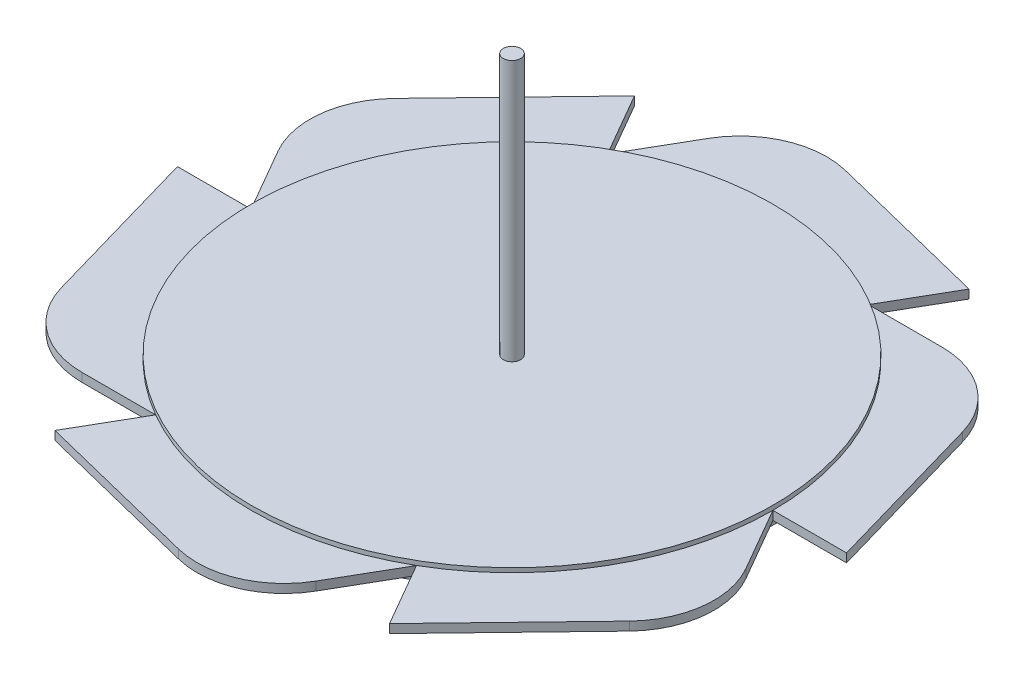
SolidWorks part; units mm, degrees
ref_plane "Front Plane" through (0, 0, 0) normal (0, 0, 1) x (1, 0, 0)
ref_plane "Top Plane" through (0, 0, 0) normal (0, 1, 0) x (1, 0, 0)
ref_plane "Right Plane" through (0, 0, 0) normal (1, 0, 0) x (0, 0, -1)
sketch "Sketch1" plane through (0, 0, 0) normal (0, 1, 0) x (1, 0, 0)
  line L0 (0, 0) -> (-7.5, 12.9904) construction
  line L1 (0, 0) -> (7.5, 12.9904) construction
  line L2 (-7.5, 12.9904) -> (7.5, 12.9904) construction
  line L3 (-7.5, 12.9904) -> (-5.3825, 16.658)
  line L4 (7.5, 12.9904) -> (9.6175, 16.658)
  line L5 (0.1538, 19.0104) -> (9.6175, 16.658)
  line L6 (7.5, 12.9904) -> (11.735, 12.9904)
  line L7 (16.5404, 9.372) -> (19.235, 0)
  line L8 (15, 0) -> (19.235, 0)
  line L9 (15, 0) -> (17.1175, -3.6677)
  line L10 (16.3866, -9.6384) -> (9.6175, -16.658)
  line L11 (7.5, -12.9904) -> (9.6175, -16.658)
  line L12 (7.5, -12.9904) -> (5.3825, -16.658)
  line L13 (-0.1538, -19.0104) -> (-9.6175, -16.658)
  line L14 (-7.5, -12.9904) -> (-9.6175, -16.658)
  line L15 (-7.5, -12.9904) -> (-11.735, -12.9904)
  line L16 (-16.5404, -9.372) -> (-19.235, 0)
  line L17 (-15, 0) -> (-19.235, 0)
  line L18 (-15, 0) -> (-17.1175, 3.6677)
  line L19 (-16.3866, 9.6384) -> (-9.6175, 16.658)
  line L20 (-7.5, 12.9904) -> (-9.6175, 16.658)
  circle A0 centre (0, 0) radius 15
  arc A1 (-5.3825, 16.658) -> (0.1538, 19.0104) centre (-1.0523, 14.158) cw
  arc A2 (11.735, 12.9904) -> (16.5404, 9.372) centre (11.735, 7.9904) cw
  arc A3 (17.1175, -3.6677) -> (16.3866, -9.6384) centre (12.7874, -6.1677) cw
  arc A4 (5.3825, -16.658) -> (-0.1538, -19.0104) centre (1.0523, -14.158) cw
  arc A5 (-11.735, -12.9904) -> (-16.5404, -9.372) centre (-11.735, -7.9904) cw
  arc A6 (-17.1175, 3.6677) -> (-16.3866, 9.6384) centre (-12.7874, 6.1677) cw
  point P9 (-3.5, 19.9186)
  point P42 (0, 0)
  dimension "D1" = 30
  dimension "D6" = 5
  dimension "D2" = 60
  dimension "D3" = 60
  dimension "D4" = 60
  dimension "D5" = 8
  dimension "D7" = 6
extrude "Boss-Extrude1" add sketch "Sketch1" along normal mid plane 1 contours A0 region at (0, 0, 0)
extrude "Boss-Extrude3" add sketch "Sketch1<3>" along normal mid plane 0.5 contours A5 L15 A0 L17 L16 | A6 L18 A0 L20 L19 | A1 L3 A0 L4 L5 | A2 L6 A0 L8 L7 | A3 L9 A0 L11 L10 | A4 L12 A0 L14 L13 region at (-13.4385, 0, -9.2457) region at (1.2878, 0, -16.261) region at (14.7263, 0, -7.0152) region at (-14.7263, 0, 7.0152) region at (13.4385, 0, 9.2457) region at (-1.2878, 0, 16.261)
sketch "Sketch1<3>" plane through (0, 0, 0) normal (0, 1, 0) x (1, 0, 0) same geometry as "Sketch1"
sketch "Sketch2" plane through (0, 0.5, 0) normal (0, 1, 0) x (1, 0, 0)
  circle A0 centre (0, 0) radius 0.5
  dimension "D1" = 1
extrude "Boss-Extrude4" add sketch "Sketch2" along normal blind 15
